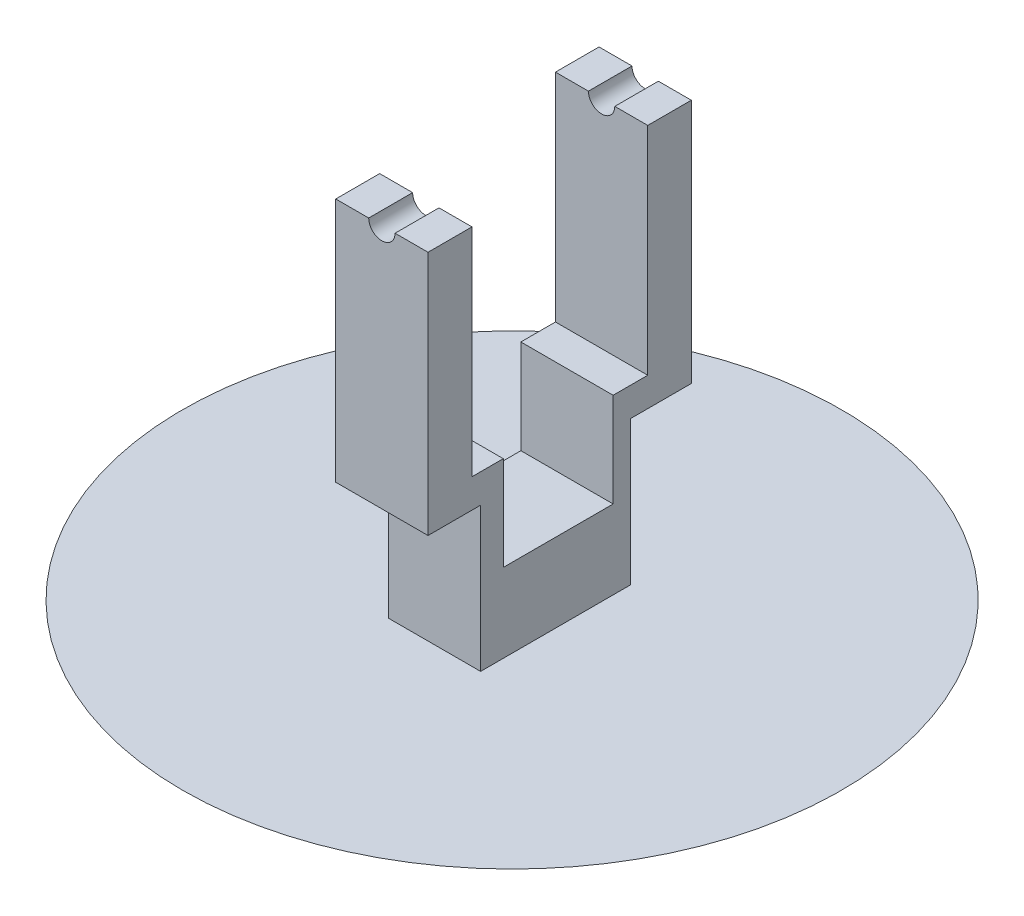
SolidWorks part; units mm, degrees
ref_plane "Front Plane" through (0, 0, 0) normal (0, 0, 1) x (1, 0, 0)
ref_plane "Top Plane" through (0, 0, 0) normal (0, 1, 0) x (1, 0, 0)
ref_plane "Right Plane" through (0, 0, 0) normal (1, 0, 0) x (0, 0, -1)
sketch "Sketch1" plane through (0, 0, 0) normal (1, 0, 0) x (0, 0, -1)
  line L0 (-59.2551, 0) -> (-39.2551, 0)
  line L1 (-39.2551, 0) -> (-39.2551, -98.4903)
  line L3 (40.7449, -98.4903) -> (40.7449, 0)
  line L4 (40.7449, 0) -> (60.5832, 0)
  line L5 (60.5832, 0) -> (60.5832, -111.6582)
  line L7 (-59.2551, -111.6582) -> (-59.2551, 0)
  line L8 (-39.2551, -98.4903) -> (-25, -98.4903)
  line L9 (-25, -98.4903) -> (-25, -141.3533)
  line L10 (-25, -141.3533) -> (25, -141.3533)
  line L11 (25, -141.3533) -> (25, -98.4903)
  line L12 (25, -98.4903) -> (40.7449, -98.4903)
  line L13 (-59.2551, -111.6582) -> (-35.3137, -111.6582)
  line L14 (-35.3137, -111.6582) -> (-35.3137, -177.1891)
  line L15 (-35.3137, -177.1891) -> (32.8724, -177.1891)
  line L16 (32.8724, -177.1891) -> (32.8724, -111.6582)
  line L17 (32.8724, -111.6582) -> (60.5832, -111.6582)
  point P13 (0, -141.3533)
  dimension "D1" = 20
  dimension "D2" = 80
  dimension "D3" = 50
extrude "Boss-Extrude1" add sketch "Sketch1" along normal mid plane 42
sketch "Sketch2" plane through (0, 0, 0) normal (0, 0, 1) x (1, 0, 0)
  line L0 (150, -177.1891) -> (79.9546, -217.1891)
  line L1 (79.9546, -217.1891) -> (0, -217.1891)
  line L2 (0, -217.1891) -> (0, -177.1891)
  line L3 (0, -177.1891) -> (150, -177.1891)
  line L5 (21, -177.1891) -> (-21, -177.1891) construction
  line L6 (0, 87.7264) -> (0, -269.6144) construction
  line L7 (21, -177.1891) -> (-21, -177.1891)
  circle A0 centre (0, 0) radius 245 construction
  dimension "D2" = 490
  dimension "D1" = 300
  dimension "D3" = 40
revolve "Revolve1" add sketch "Sketch2" angle 360 about L6 region at (59.2667, -195.1584, 0)
sketch "Sketch3" plane through (0, 0, 0) normal (0, 0, 1) x (1, 0, 0)
  circle A0 centre (0, 0) radius 6
  dimension "D1" = 12
extrude "Cut-Extrude1" cut sketch "Sketch3" against normal through all both and the other way through all
